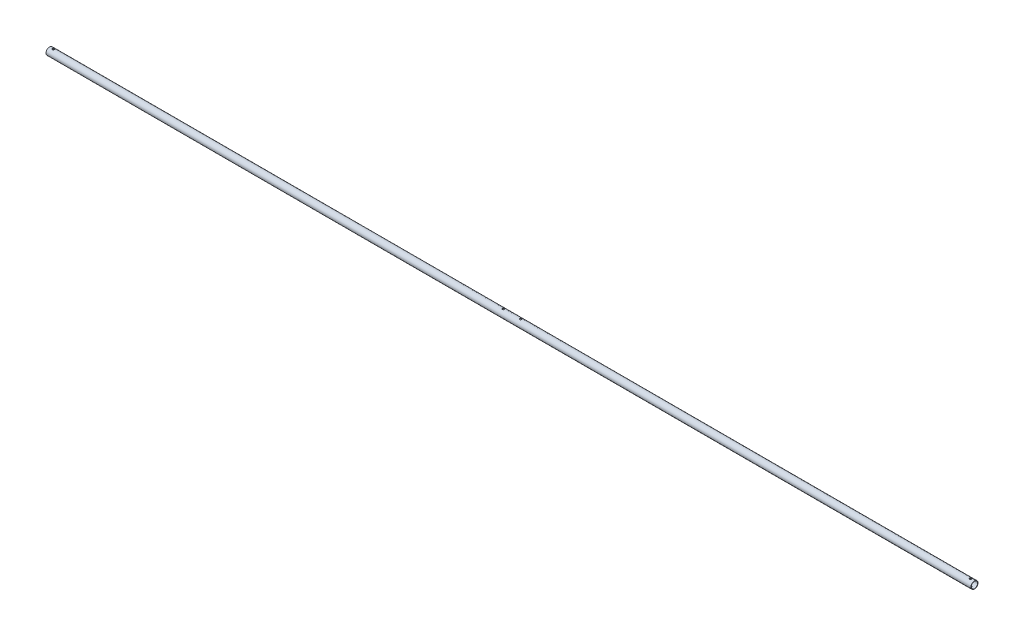
SolidWorks part; units mm, degrees
material "Galvanized Steel"
ref_plane "Front Plane" through (0, 0, 0) normal (0, 0, 1) x (1, 0, 0)
ref_plane "Top Plane" through (0, 0, 0) normal (0, 1, 0) x (1, 0, 0)
ref_plane "Right Plane" through (0, 0, 0) normal (1, 0, 0) x (0, 0, -1)
sketch "Sketch3" plane through (0, 0, 0) normal (1, 0, 0) x (0, 0, -1)
  circle A0 centre (0, 0) radius 10.4648
  circle A1 centre (0, 0) radius 11.7094
  dimension "D1" = 20.9296
  dimension "D2" = 23.4188
extrude "Boss-Extrude1" add sketch "Sketch3" along normal blind 3048
sketch "Sketch4" plane through (0, 0, 0) normal (0, 1, 0) x (1, 0, 0)
  circle A0 centre (1495.425, 0) radius 3.175
  circle A1 centre (1552.575, 0) radius 3.175
  point P0 (1524, 0)
  point P1 (1552.575, 0)
  point P3 (1495.425, 0)
  dimension "D4" = 6.35
  dimension "D5" = 6.35
  dimension "D1" = 1524
  dimension "D2" = 28.575
  dimension "D3" = 28.575
extrude "Cut-Extrude1" cut sketch "Sketch4" against normal through all and the other way through all
sketch "Sketch5" plane through (0, 0, 0) normal (0, 1, 0) x (1, 0, 0)
  line L0 (3048, -11.7094) -> (3048, 11.7094) construction
  circle A0 centre (12.7, 0) radius 3.175
  circle A1 centre (3035.3, 0) radius 3.175
  point P0 (12.7, 0)
  point P4 (3035.3, 0)
  dimension "D2" = 6.35
  dimension "D4" = 6.35
  dimension "D1" = 12.7
  dimension "D3" = 12.7
extrude "Cut-Extrude2" cut sketch "Sketch5" against normal through all and the other way through all
